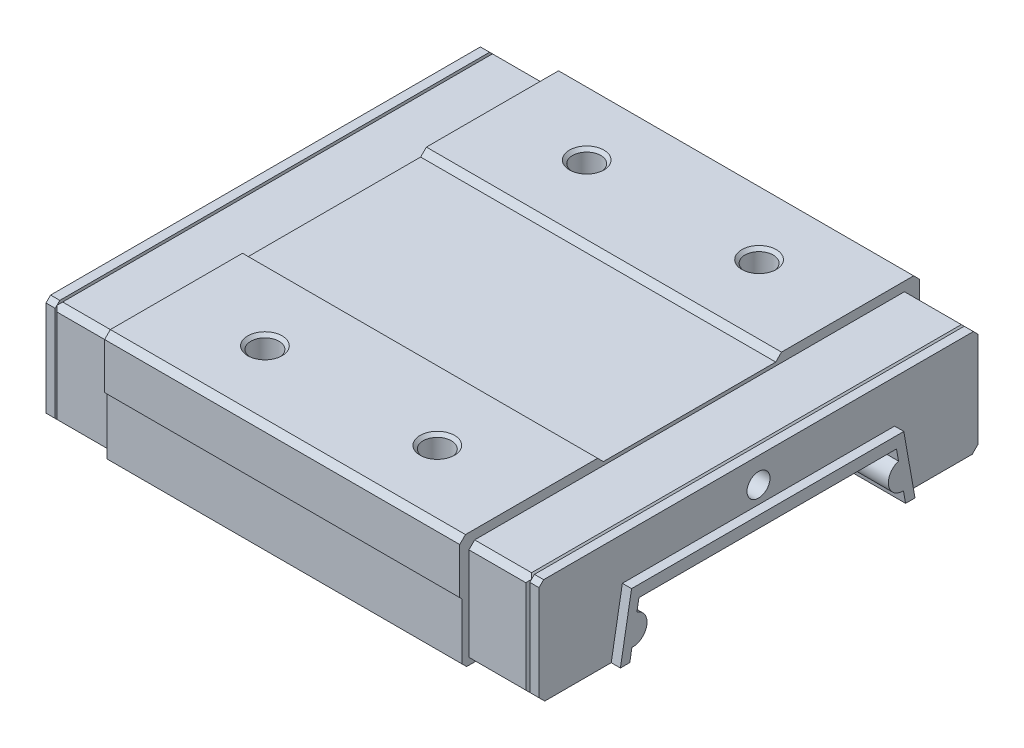
SolidWorks part; units mm, degrees
ref_plane "Plano frontal" through (0, 0, 0) normal (0, 0, 1) x (1, 0, 0)
ref_plane "Plano superior" through (0, 0, 0) normal (0, 1, 0) x (1, 0, 0)
ref_plane "Plano direito" through (0, 0, 0) normal (1, 0, 0) x (0, 0, -1)
ref_plane "Plano1" through (0, 0, 0) normal (1, 0, 0) x (0, 0, -1)
sketch "Esboço1" plane through (0, 0, 0) normal (1, 0, 0) x (0, 0, -1)
  line L0 (-20, 9.5) -> (-20, 5.5)
  line L1 (-20, 5.5) -> (-19.8, 5.3)
  line L2 (-19.8, 5.3) -> (-19.8, 0.4)
  line L3 (-19.8, 0.4) -> (-19.4, 0)
  line L4 (-19.4, 0) -> (19.4, 0)
  line L5 (19.4, 0) -> (19.8, 0.4)
  line L6 (19.8, 0.4) -> (19.8, 5.3)
  line L7 (19.8, 5.3) -> (20, 5.5)
  line L8 (20, 5.5) -> (20, 9.5)
  line L9 (20, 9.5) -> (19.5, 10)
  line L10 (19.5, 10) -> (8, 10)
  line L11 (8, 10) -> (7.5, 9.5)
  line L12 (7.5, 9.5) -> (-7.5, 9.5)
  line L13 (-7.5, 9.5) -> (-8, 10)
  line L14 (-8, 10) -> (-19.5, 10)
  line L15 (-19.5, 10) -> (-20, 9.5)
extrude "Ressalto-extrusão1" add sketch "Esboço1" against normal blind 15.45 and the other way blind 15.45
ref_plane "Plano2" through (-15.45, 0, 0) normal (1, 0, 0) x (0, 0, -1)
sketch "Esboço2" plane through (-15.45, 0, 0) normal (1, 0, 0) x (0, 0, -1)
  line L0 (-19.2, 8.7) -> (-19.2, 0.6)
  line L1 (-19.2, 0.6) -> (-18.6, 0)
  line L2 (-18.6, 0) -> (18.6, 0)
  line L3 (18.6, 0) -> (19.2, 0.6)
  line L4 (19.2, 0.6) -> (19.2, 8.7)
  line L5 (19.2, 8.7) -> (18.7, 9.2)
  line L6 (18.7, 9.2) -> (-18.7, 9.2)
  line L7 (-18.7, 9.2) -> (-19.2, 8.7)
extrude "Ressalto-extrusão2" add sketch "Esboço2" against normal blind 6
ref_plane "Plano3" through (15.45, 0, 0) normal (1, 0, 0) x (0, 0, -1)
sketch "Esboço3" plane through (15.45, 0, 0) normal (1, 0, 0) x (0, 0, -1)
  line L0 (-19.2, 8.7) -> (-19.2, 0.6)
  line L1 (-19.2, 0.6) -> (-18.6, 0)
  line L2 (-18.6, 0) -> (18.6, 0)
  line L3 (18.6, 0) -> (19.2, 0.6)
  line L4 (19.2, 0.6) -> (19.2, 8.7)
  line L5 (19.2, 8.7) -> (18.7, 9.2)
  line L6 (18.7, 9.2) -> (-18.7, 9.2)
  line L7 (-18.7, 9.2) -> (-19.2, 8.7)
extrude "Ressalto-extrusão3" add sketch "Esboço3" along normal blind 6
ref_plane "Plano4" through (0, 0, 0) normal (1, 0, 0) x (0, 0, -1)
sketch "Esboço4" plane through (0, 0, 0) normal (1, 0, 0) x (0, 0, -1)
  line L0 (-12.816, 0) -> (12.816, 0)
  line L1 (12.816, 0) -> (11.8462, 5.5)
  line L2 (11.8462, 5.5) -> (-11.8462, 5.5)
  line L3 (-11.8462, 5.5) -> (-12.816, 0)
extrude "Ressalto-extrusão4" add sketch "Esboço4" against normal blind 22.25 and the other way blind 22.25
ref_plane "Plano5" through (0, 0, 0) normal (1, 0, 0) x (0, 0, -1)
sketch "Esboço5" plane through (0, 0, 0) normal (1, 0, 0) x (0, 0, -1)
  line L0 (-12, 0) -> (12, 0)
  line L1 (12, 0) -> (11.8146, 1.0517)
  line L2 (11.3837, 3.4951) -> (11.2065, 4.5)
  line L3 (11.2065, 4.5) -> (-11.2065, 4.5)
  line L4 (-11.2065, 4.5) -> (-11.3837, 3.4951)
  line L5 (-11.8146, 1.0517) -> (-12, 0)
  arc A0 (11.8146, 1.0517) -> (11.3837, 3.4951) centre (11.75, 2.3) cw
  arc A1 (-11.3837, 3.4951) -> (-11.8146, 1.0517) centre (-11.75, 2.3) cw
extrude "Corte-extrusão1" cut sketch "Esboço5" against normal blind 22.25 and the other way blind 22.25
ref_plane "Plano6" through (0, 0, 14) normal (0, 0, 1) x (1, 0, 0)
sketch "Esboço6" plane through (0, 0, 14) normal (0, 0, 1) x (1, 0, 0)
  line L0 (7.5, 10) -> (9, 10)
  line L1 (9, 10) -> (8.7295, 9.7295)
  line L2 (8.7295, 9.7295) -> (8.7295, 5.8)
  line L3 (8.7295, 5.8) -> (7.5, 5.0901)
  line L4 (7.5, 5.0901) -> (7.5, 10)
  line L5 (7.5, 5.0901) -> (7.5, 10) construction
revolve "Corte-Revolução1" cut sketch "Esboço6" angle 360 about L5 reverse direction yes
ref_plane "Plano7" through (0, 0, -14) normal (0, 0, 1) x (1, 0, 0)
sketch "Esboço7" plane through (0, 0, -14) normal (0, 0, 1) x (1, 0, 0)
  line L0 (-7.5, 10) -> (-6, 10)
  line L1 (-6, 10) -> (-6.2705, 9.7295)
  line L2 (-6.2705, 9.7295) -> (-6.2705, 5.8)
  line L3 (-6.2705, 5.8) -> (-7.5, 5.0901)
  line L4 (-7.5, 5.0901) -> (-7.5, 10)
  line L5 (-7.5, 5.0901) -> (-7.5, 10) construction
revolve "Corte-Revolução2" cut sketch "Esboço7" angle 360 about L5 reverse direction yes
ref_plane "Plano8" through (0, 0, 14) normal (0, 0, 1) x (1, 0, 0)
sketch "Esboço8" plane through (0, 0, 14) normal (0, 0, 1) x (1, 0, 0)
  line L0 (-7.5, 10) -> (-6, 10)
  line L1 (-6, 10) -> (-6.2705, 9.7295)
  line L2 (-6.2705, 9.7295) -> (-6.2705, 5.8)
  line L3 (-6.2705, 5.8) -> (-7.5, 5.0901)
  line L4 (-7.5, 5.0901) -> (-7.5, 10)
  line L5 (-7.5, 5.0901) -> (-7.5, 10) construction
revolve "Corte-Revolução3" cut sketch "Esboço8" angle 360 about L5 reverse direction yes
ref_plane "Plano9" through (0, 0, -14) normal (0, 0, 1) x (1, 0, 0)
sketch "Esboço9" plane through (0, 0, -14) normal (0, 0, 1) x (1, 0, 0)
  line L0 (7.5, 10) -> (9, 10)
  line L1 (9, 10) -> (8.7295, 9.7295)
  line L2 (8.7295, 9.7295) -> (8.7295, 5.8)
  line L3 (8.7295, 5.8) -> (7.5, 5.0901)
  line L4 (7.5, 5.0901) -> (7.5, 10)
  line L5 (7.5, 5.0901) -> (7.5, 10) construction
revolve "Corte-Revolução4" cut sketch "Esboço9" angle 360 about L5 reverse direction yes
ref_plane "Plano10" through (0, 0, 0) normal (0, 1, 0) x (1, 0, 0)
sketch "Esboço10" plane through (0, 0, 0) normal (0, 1, 0) x (1, 0, 0)
  line L0 (-24.25, -22) -> (24.25, -22)
  line L1 (24.25, -22) -> (24.25, 22)
  line L2 (24.25, 22) -> (-24.25, 22)
  line L3 (-24.25, 22) -> (-24.25, -22)
  line L4 (-23.25, 19.1) -> (-23.25, -19.1)
  line L5 (-23.25, -19.1) -> (-20.65, -19.1)
  line L6 (-20.65, -19.1) -> (-20.65, -21)
  line L7 (-20.65, -21) -> (20.65, -21)
  line L8 (20.65, -21) -> (20.65, -19.1)
  line L9 (20.65, -19.1) -> (23.25, -19.1)
  line L10 (23.25, -19.1) -> (23.25, 19.1)
  line L11 (23.25, 19.1) -> (20.65, 19.1)
  line L12 (20.65, 19.1) -> (20.65, 21)
  line L13 (20.65, 21) -> (-20.65, 21)
  line L14 (-20.65, 21) -> (-20.65, 19.1)
  line L15 (-20.65, 19.1) -> (-23.25, 19.1)
extrude "Corte-extrusão2" cut sketch "Esboço10" along normal blind 11
ref_plane "Plano11" through (0, 0, 0) normal (0, 0, 1) x (1, 0, 0)
sketch "Esboço11" plane through (0, 0, 0) normal (0, 0, 1) x (1, 0, 0)
  line L0 (-20.65, 9.2) -> (-20.65, 8.95)
  line L1 (-20.65, 8.95) -> (-20.4, 9.2)
  line L2 (-20.4, 9.2) -> (-20.65, 9.2)
extrude "Corte-extrusão3" cut sketch "Esboço11" against normal blind 20 and the other way blind 20
ref_plane "Plano12" through (0, 0, 0) normal (0, 0, 1) x (1, 0, 0)
sketch "Esboço12" plane through (0, 0, 0) normal (0, 0, 1) x (1, 0, 0)
  line L0 (20.4, 9.2) -> (20.65, 8.95)
  line L1 (20.65, 8.95) -> (20.65, 9.2)
  line L2 (20.65, 9.2) -> (20.4, 9.2)
extrude "Corte-extrusão4" cut sketch "Esboço12" against normal blind 20 and the other way blind 20
ref_plane "Plano13" through (0, 0, 0) normal (0, 1, 0) x (1, 0, 0)
sketch "Esboço13" plane through (0, 0, 0) normal (0, 1, 0) x (1, 0, 0)
  line L0 (-20.65, 19.2) -> (-20.65, 18.95)
  line L1 (-20.65, 18.95) -> (-20.4, 19.2)
  line L2 (-20.4, 19.2) -> (-20.65, 19.2)
extrude "Corte-extrusão5" cut sketch "Esboço13" along normal blind 10
ref_plane "Plano14" through (0, 0, 0) normal (0, 1, 0) x (1, 0, 0)
sketch "Esboço14" plane through (0, 0, 0) normal (0, 1, 0) x (1, 0, 0)
  line L0 (-20.65, -19.2) -> (-20.4, -19.2)
  line L1 (-20.4, -19.2) -> (-20.65, -18.95)
  line L2 (-20.65, -18.95) -> (-20.65, -19.2)
extrude "Corte-extrusão6" cut sketch "Esboço14" along normal blind 10
ref_plane "Plano15" through (0, 0, 0) normal (0, 1, 0) x (1, 0, 0)
sketch "Esboço15" plane through (0, 0, 0) normal (0, 1, 0) x (1, 0, 0)
  line L0 (20.4, 19.2) -> (20.65, 18.95)
  line L1 (20.65, 18.95) -> (20.65, 19.2)
  line L2 (20.65, 19.2) -> (20.4, 19.2)
extrude "Corte-extrusão7" cut sketch "Esboço15" along normal blind 10
ref_plane "Plano16" through (0, 0, 0) normal (0, 1, 0) x (1, 0, 0)
sketch "Esboço16" plane through (0, 0, 0) normal (0, 1, 0) x (1, 0, 0)
  line L0 (20.4, -19.2) -> (20.65, -19.2)
  line L1 (20.65, -19.2) -> (20.65, -18.95)
  line L2 (20.65, -18.95) -> (20.4, -19.2)
extrude "Corte-extrusão8" cut sketch "Esboço16" along normal blind 10
ref_plane "Plano17" through (0, 0, 0) normal (0, 0, 1) x (1, 0, 0)
sketch "Esboço17" plane through (0, 0, 0) normal (0, 0, 1) x (1, 0, 0)
  line L0 (-21.45, 7) -> (-21.45, 8)
  line L1 (-21.45, 8) -> (-18.95, 8)
  line L2 (-18.95, 8) -> (-18.95, 7)
  line L3 (-18.95, 7) -> (-21.45, 7)
  line L4 (-18.95, 7) -> (-21.45, 7) construction
revolve "Corte-Revolução5" cut sketch "Esboço17" angle 360 about L4 reverse direction yes
ref_plane "Plano18" through (0, 0, 0) normal (0, 0, 1) x (1, 0, 0)
sketch "Esboço18" plane through (0, 0, 0) normal (0, 0, 1) x (1, 0, 0)
  line L0 (18.95, 7) -> (18.95, 8)
  line L1 (18.95, 8) -> (21.45, 8)
  line L2 (21.45, 8) -> (21.45, 7)
  line L3 (21.45, 7) -> (18.95, 7)
  line L4 (21.45, 7) -> (18.95, 7) construction
revolve "Corte-Revolução6" cut sketch "Esboço18" angle 360 about L4 reverse direction yes
sketch "Esboço19" plane through (0, 9.5, 0) normal (0, 1, 0) x (1, 0, 0)
  line L0 (15.45, 0) -> (-15.45, 0) construction
  line L1 (15.45, 7.5) -> (15.45, -7.5) construction
  line L2 (-15.45, 7.5) -> (-15.45, -7.5) construction
  line L4 (15.45, -7.5) -> (-15.45, -7.5) construction
  line L5 (0, -7.5) -> (0, 7.5) construction
  line L6 (15.45, 7.5) -> (-15.45, 7.5) construction
  circle A0 centre (0, 0) radius 3.6906
